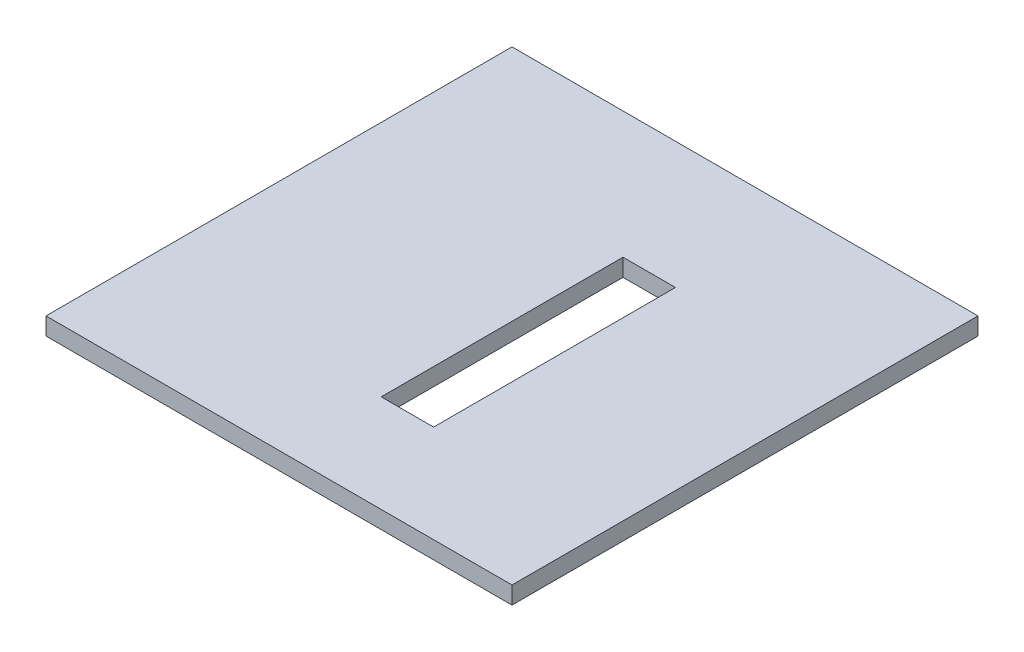
SolidWorks part; units mm, degrees
ref_plane "Front Plane" through (0, 0, 0) normal (0, 0, 1) x (1, 0, 0)
ref_plane "Top Plane" through (0, 0, 0) normal (0, 1, 0) x (1, 0, 0)
ref_plane "Right Plane" through (0, 0, 0) normal (1, 0, 0) x (0, 0, -1)
sketch "Sketch1" plane through (0, 0, 0) normal (0, 1, 0) x (1, 0, 0)
  line L0 (80, 0) -> (80, 80) construction
  line L1 (0, 0) -> (80, 0)
  line L2 (0, 0) -> (0, 80)
  line L3 (0, 80) -> (80, 80)
  line L4 (80, 0) -> (80, 80)
  line L5 (80, 80) -> (0, 80) construction
  line L7 (40.8, 16.7443) -> (49.8, 16.7443)
  line L8 (40.8, 16.7443) -> (40.8, 58.2557)
  line L9 (40.8, 58.2557) -> (49.8, 58.2557)
  line L10 (49.8, 16.7443) -> (49.8, 58.2557)
  line L12 (46.8, 16.7443) -> (46.8, 58.2557) construction
  line L13 (43.8, 58.2557) -> (43.8, 16.7443) construction
  line L14 (46.8, 16.5) -> (46.8, 58.5) construction
  line L15 (43.8, 16.5) -> (43.8, 58.5) construction
  line L17 (46.8, 37.5) -> (49.8, 37.5) construction
  line L18 (43.8, 40) -> (40.8, 40) construction
  line L20 (43.8, 37.5) -> (40.8, 37.5) construction
sketch "Sketch2" plane through (0, 0, 0) normal (0, 0, 1) x (1, 0, 0)
  line L1 (0, 0) -> (80, 0)
  line L2 (0, 0) -> (0, -3)
  line L3 (0, -3) -> (80, -3)
  line L4 (80, 0) -> (80, -3)
extrude "Boss-Extrude1" add sketch "Sketch1" against normal up to vertex (3 mm away) up to point (0, -3, 0)
